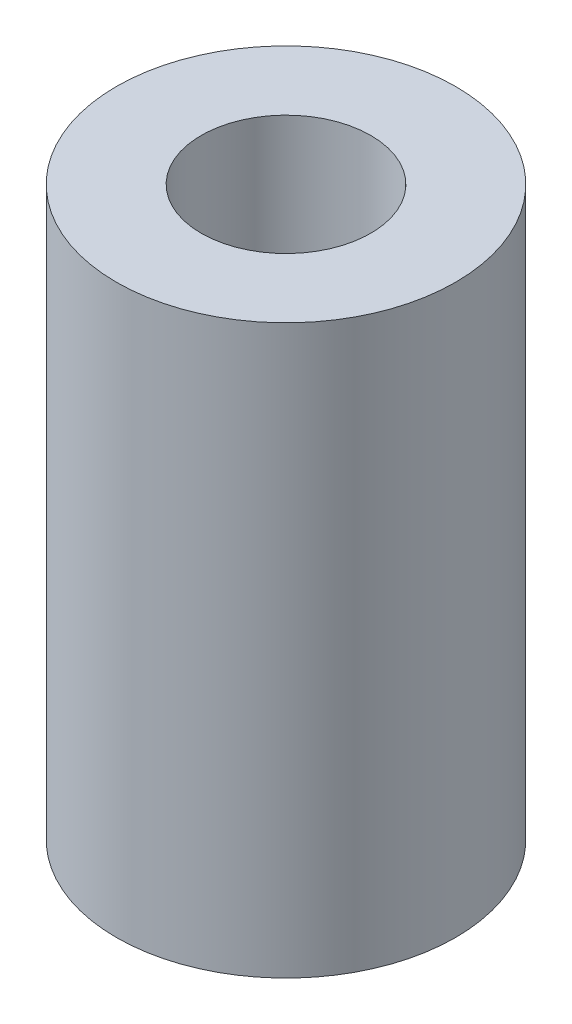
SolidWorks part; units mm, degrees
ref_plane "Front Plane" through (0, 0, 0) normal (0, 0, 1) x (1, 0, 0)
ref_plane "Top Plane" through (0, 0, 0) normal (0, 1, 0) x (1, 0, 0)
ref_plane "Right Plane" through (0, 0, 0) normal (1, 0, 0) x (0, 0, -1)
sketch "Sketch1" plane through (0, 0, 0) normal (0, 1, 0) x (1, 0, 0)
  circle A0 centre (0, 0) radius 4.5
  circle A1 centre (0, 0) radius 2.25
  dimension "D1" = 9
  dimension "D2" = 4.5
extrude "Boss-Extrude1" add sketch "Sketch1" along normal blind 15.06
